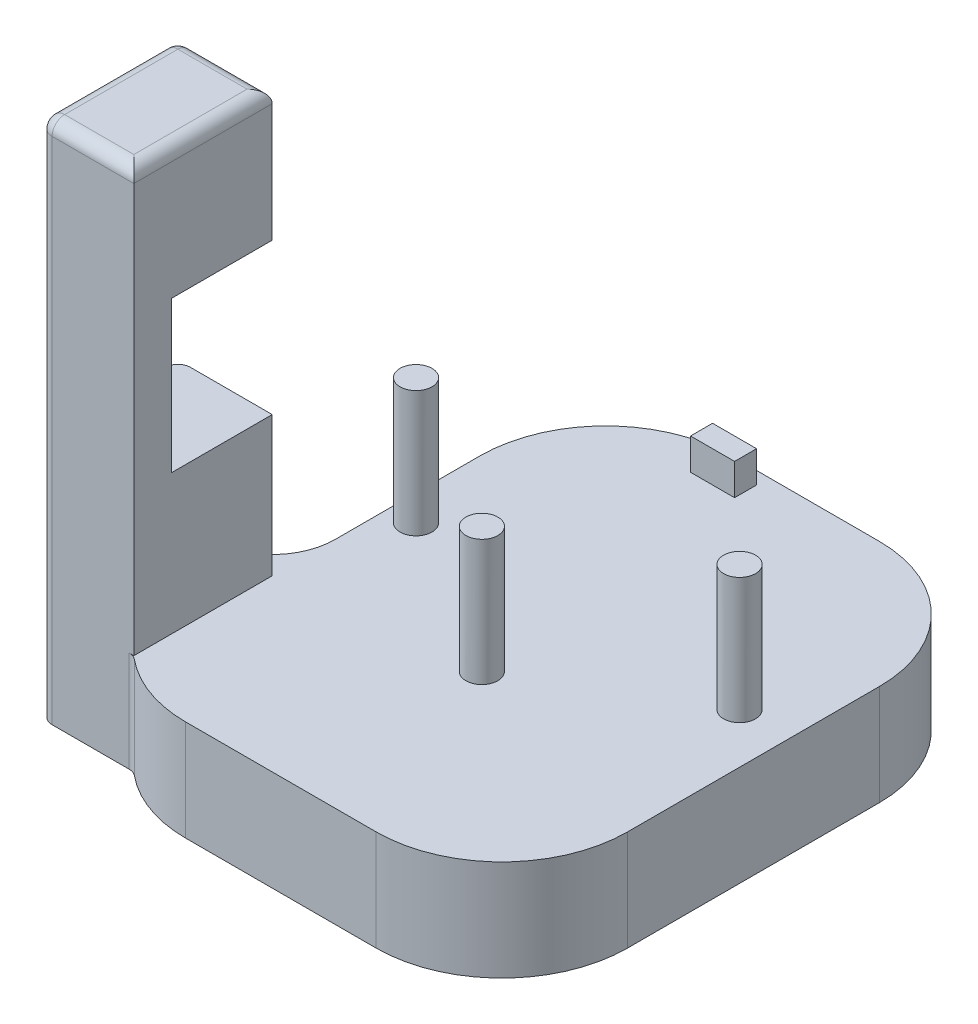
SolidWorks part; units mm, degrees
ref_plane "Front Plane" through (0, 0, 0) normal (0, 0, 1) x (1, 0, 0)
ref_plane "Top Plane" through (0, 0, 0) normal (0, 1, 0) x (1, 0, 0)
ref_plane "Right Plane" through (0, 0, 0) normal (1, 0, 0) x (0, 0, -1)
sketch "Sketch5" plane through (0, 0, 0) normal (0, 1, 0) x (1, 0, 0)
  line L1 (31.75, 40) -> (-31.75, 40)
  line L2 (31.75, 40) -> (31.75, -40)
  line L3 (31.75, -40) -> (-31.75, -40)
  line L4 (-31.75, 40) -> (-31.75, -40)
  line L5 (31.75, 40) -> (-31.75, -40) construction
  line L6 (31.75, -40) -> (-31.75, 40) construction
  point P0 (0, 0)
  dimension "D1" = 80
  dimension "D2" = 63.5
extrude "Boss-Extrude4" add sketch "Sketch5" along normal blind 16
sketch "Sketch6" plane through (0, 16, 0) normal (0, 1, 0) x (1, 0, 0)
  line L0 (31.75, 40) -> (-31.75, 40) construction
  line L1 (-5.75, 38) -> (-12.75, 38)
  line L2 (-5.75, 38) -> (-5.75, 34.5)
  line L3 (-5.75, 34.5) -> (-12.75, 34.5)
  line L4 (-12.75, 38) -> (-12.75, 34.5)
  line L5 (-5.75, 38) -> (-12.75, 34.5) construction
  line L6 (-5.75, 34.5) -> (-12.75, 38) construction
  line L9 (0, 0) -> (0, 40) construction
  line L10 (-31.75, 40) -> (-31.75, -40) construction
  point P0 (-9.25, 36.25)
  dimension "D1" = 7
  dimension "D2" = 3.5
  dimension "D3" = 2
  dimension "D4" = 19
extrude "Boss-Extrude5" add sketch "Sketch6" along normal blind 5 contours L3 L4 L1 L2
sketch "Sketch9" plane through (0, 0, 0) normal (0, 1, 0) x (1, 0, 0)
  line L0 (-31.75, 40) -> (-31.75, -40) construction
  line L5 (-31.75, -35) -> (-46.75, -35)
  line L6 (-31.75, -35) -> (-31.75, -13)
  line L7 (-31.75, -13) -> (-46.75, -13)
  line L8 (-46.75, -35) -> (-46.75, -13)
  line L9 (-31.75, -40) -> (31.75, -40) construction
  point P13 (-39.25, -13)
  dimension "D4" = 5
  dimension "D5" = 22
  dimension "D6" = 7.5
sketch "Sketch13" plane through (0, 16, 0) normal (0, 1, 0) x (1, 0, 0)
  line L0 (-31.75, 40) -> (-31.75, -40) construction
  line L2 (-31.75, -40) -> (31.75, -40) construction
  circle A0 centre (-27.6098, 5.72) radius 2.54
  circle A1 centre (23.8252, 5.72) radius 2.54
  circle A2 centre (-1.905, -9.52) radius 2.54
  dimension "D1" = 4.1402
  dimension "D3" = 5.08
  dimension "D4" = 51.435
  dimension "D6" = 5.08
  dimension "D7" = 5.08
  dimension "D2" = 45.72
  dimension "D5" = 45.72
  dimension "D8" = 25.7048
  dimension "D9" = 15.24
extrude "Boss-Extrude8" add sketch "Sketch13" along normal blind 20
extrude "Boss-Extrude10" add sketch "Sketch9" along normal blind 83 contours L8 L7 L6 L5
sketch "Sketch14" plane through (0, 0, 13) normal (0, 0, -1) x (-1, 0, 0)
  line L0 (31.75, 83) -> (31.75, 16) construction
  line L1 (31.75, 38.2) -> (46.75, 38.2)
  line L2 (31.75, 38.2) -> (31.75, 62.2)
  line L3 (31.75, 62.2) -> (46.75, 62.2)
  line L4 (46.75, 38.2) -> (46.75, 62.2)
  line L5 (46.75, 83) -> (46.75, 0) construction
  line L6 (31.75, 83) -> (46.75, 83) construction
  dimension "D1" = 20.8
  dimension "D2" = 24
extrude "Cut-Extrude1" cut sketch "Sketch14" against normal blind 16 contours L3 L4 L1 L2
fillet "Fillet1" radius 20 4 edges at (-31.75, 8, -40) (31.75, 8, -40) (-31.75, 8, 40) (31.75, 8, 40)
fillet "Fillet2" radius 10 1 edges at (-31.75, 8, 13)
fillet "Fillet3" radius 2 3 edges at (-31.75, 8, 35) (-46.75, 41.5, 35) (-46.75, 19.1, 13)
fillet "Fillet4" radius 2 1 edges at (-46.75, 72.6, 13)
fillet "Fillet6" radius 2 6 edges at (-31.75, 83, 24) (-38.25, 83, 35) (-46.1642, 83, 34.4142) (-46.75, 83, 24) (-46.1642, 83, 13.5858) (-38.25, 83, 13)
